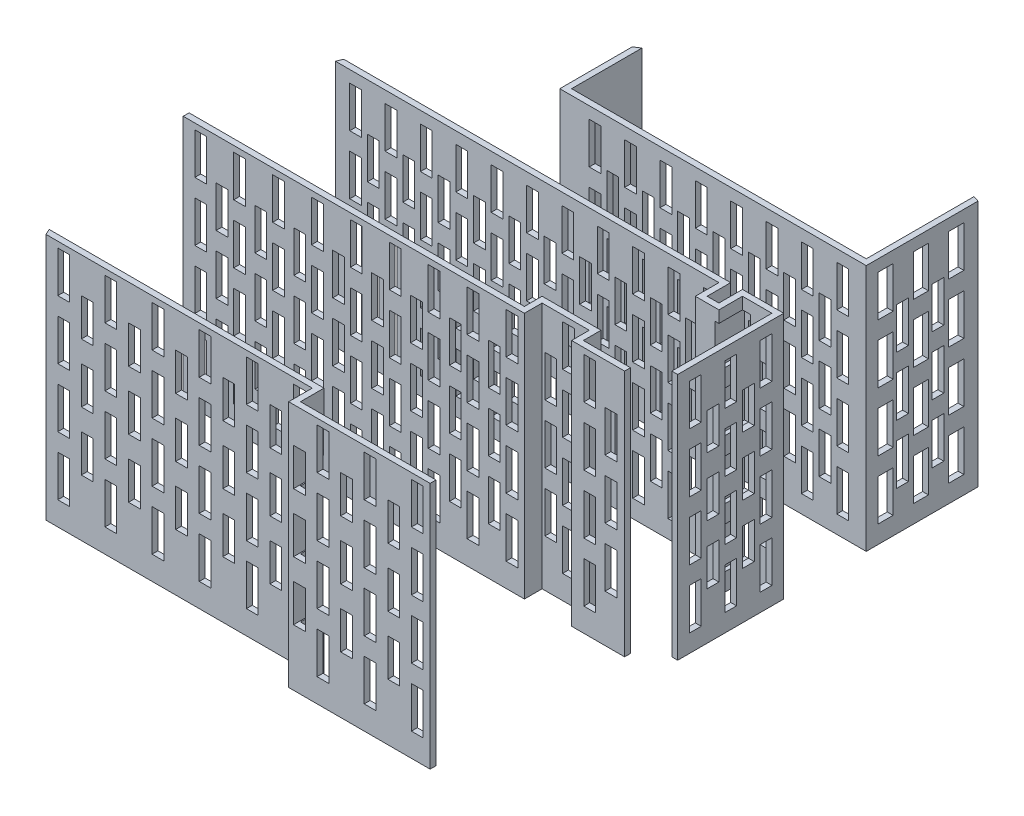
SolidWorks part; units mm, degrees
ref_plane "前视基准面" through (0, 0, 0) normal (0, 0, 1) x (1, 0, 0)
ref_plane "上视基准面" through (0, 0, 0) normal (0, 1, 0) x (1, 0, 0)
ref_plane "右视基准面" through (0, 0, 0) normal (1, 0, 0) x (0, 0, -1)
sketch "草图1" plane through (0, 0, 0) normal (0, 1, 0) x (1, 0, 0)
  line L0 (9, 42.9063) -> (9, -40.9545) construction
  line L1 (-51.5032, -25) -> (46.7174, -25) construction
  line L2 (-16, 25.9663) -> (-16, 20)
  line L3 (-16, 20) -> (9, 20)
  line L4 (-27.5908, -13) -> (-5, -13)
  line L5 (-5, -13) -> (-5, -15)
  line L6 (-5, -15) -> (7, -15)
  line L7 (-28.0401, 12) -> (4.5, 12)
  line L8 (4.5, 12) -> (4.5, 10)
  line L9 (4.5, 10) -> (6.5, 10)
  line L10 (6.5, 10) -> (6.5, 12)
  line L11 (6.5, 12) -> (9, 12)
  line L12 (9, 12) -> (9, 3.5009)
  line L13 (7, 2) -> (3, 2)
  line L14 (3, 2) -> (3, 3.5)
  line L15 (3, 3.5) -> (-2, 3.5)
  line L16 (-2, 3.5) -> (-2, 2)
  line L17 (-2, 2) -> (-30.4344, 2)
  line L18 (9, 20) -> (9, 29.1419)
  line L19 (-16.5, 25.6515) -> (-16.5, 19.5)
  line L20 (-16.5, 19.5) -> (9.5, 19.5)
  line L21 (9.5, 19.5) -> (9.5, 28.9828)
  line L22 (-16.5, 25.9663) -> (-16.5, 19.5) construction
  line L23 (9.5, 19.5) -> (9.5, 29.1419) construction
  line L24 (9, 29.1419) -> (9.5, 28.9828)
  line L25 (7, 3.5009) -> (9, 3.5009) construction
  line L26 (7, 3.5009) -> (7, 2) construction
  line L27 (7, -16.4991) -> (9, -16.4991) construction
  line L28 (7, -6.5) -> (19.2918, -6.5)
  line L29 (7, -15) -> (7, -16.4991) construction
  line L30 (-27.8209, 12.5) -> (5, 12.5)
  line L31 (5, 12.5) -> (5, 10.5)
  line L32 (5, 10.5) -> (6, 10.5)
  line L33 (6, 10.5) -> (6, 12.5)
  line L34 (6, 12.5) -> (9.5, 12.5)
  line L35 (9.5, 12.5) -> (9.5, 3.5009)
  line L36 (7, 1.5) -> (2.5, 1.5)
  line L37 (2.5, 1.5) -> (2.5, 3)
  line L38 (2.5, 3) -> (-1.5, 3)
  line L39 (-1.5, 3) -> (-1.5, 1.5)
  line L40 (-1.5, 1.5) -> (-30.4631, 1.5)
  line L41 (9, 3.5009) -> (9.5, 3.5009)
  line L42 (7, 1.5) -> (7, 2)
  line L43 (-28.0401, 12.5) -> (5, 12.5) construction
  line L44 (-1.5, 1.5) -> (-30.4344, 1.5) construction
  line L45 (-27.8209, -12.5) -> (-4.5, -12.5)
  line L46 (-4.5, -12.5) -> (-4.5, -14.5)
  line L47 (-4.5, -14.5) -> (7, -14.5)
  line L48 (7, -14.5) -> (7, -15)
  line L49 (-27.5908, -12.5) -> (-4.5, -12.5) construction
  arc A0 (-16, 25.9663) -> (-16.5, 25.6515) centre (0, 0) ccw
  arc A1 (-27.8209, -12.5) -> (-27.5908, -13) centre (0, 0) ccw
  arc A2 (-30.4344, 2) -> (-30.4631, 1.5) centre (0, 0) ccw
  arc A3 (-27.8209, 12.5) -> (-28.0401, 12) centre (0, 0) ccw
  dimension "D1" = 61
  dimension "D2" = 9
  dimension "D3" = 25
  dimension "D4" = 25
  dimension "D5" = 45
  dimension "D6" = 14
  dimension "D7" = 12
  dimension "D8" = 10
  dimension "D9" = 15
  dimension "D10" = 1.5
  dimension "D11" = 5
  dimension "D12" = 6
  dimension "D13" = 2
  dimension "D14" = 2
  dimension "D15" = 2.5
  dimension "D16" = 10
  dimension "D18" = 9.4828
  dimension "D19" = 6.5
  dimension "D20" = 10.0009
  dimension "D21" = 2
  dimension "D22" = 9.9991
  dimension "D17" = 0.5
  dimension "D23" = 0.5
  dimension "D24" = 0.5
extrude "凸台-拉伸1" add sketch "草图1" along normal blind 21 contours L6 L48 L47 L46 L45 A1 L4 L5 | L15 L16 L17 A2 L40 L39 L38 L37 L36 L42 L13 L14 | L35 L41 L12 L11 L10 L9 L8 L7 A3 L30 L31 L32 L33 L34 | L20 L21 L24 L18 L3 L2 A0 L19
sketch "草图3" plane through (0, 0, 15) normal (0, 0, 1) x (1, 0, 0)
  line L0 (-27.5908, 21) -> (-5, 21) construction
  line L1 (-26.5908, 20.5) -> (-25.5908, 20.5)
  line L2 (-26.5908, 20.5) -> (-26.5908, 17)
  line L3 (-26.5908, 17) -> (-25.5908, 17)
  line L4 (-25.5908, 20.5) -> (-25.5908, 17)
  line L5 (-27.5908, 21) -> (-27.5908, 0) construction
  line L6 (-22.5908, 20.5) -> (-22.5908, 17)
  line L7 (-22.5908, 20.5) -> (-21.5908, 20.5)
  line L8 (-21.5908, 20.5) -> (-21.5908, 17)
  line L9 (-22.5908, 17) -> (-21.5908, 17)
  line L10 (-18.5908, 20.5) -> (-18.5908, 17)
  line L11 (-18.5908, 20.5) -> (-17.5908, 20.5)
  line L12 (-17.5908, 20.5) -> (-17.5908, 17)
  line L13 (-18.5908, 17) -> (-17.5908, 17)
  line L14 (-14.5908, 20.5) -> (-14.5908, 17)
  line L15 (-14.5908, 20.5) -> (-13.5908, 20.5)
  line L16 (-13.5908, 20.5) -> (-13.5908, 17)
  line L17 (-14.5908, 17) -> (-13.5908, 17)
  line L18 (-10.5908, 20.5) -> (-10.5908, 17)
  line L19 (-10.5908, 20.5) -> (-9.5908, 20.5)
  line L20 (-9.5908, 20.5) -> (-9.5908, 17)
  line L21 (-10.5908, 17) -> (-9.5908, 17)
  line L22 (-6.5908, 20.5) -> (-6.5908, 17)
  line L23 (-6.5908, 20.5) -> (-5.5908, 20.5)
  line L24 (-5.5908, 20.5) -> (-5.5908, 17)
  line L25 (-6.5908, 17) -> (-5.5908, 17)
  line L26 (-2.5908, 20.5) -> (-2.5908, 17)
  line L27 (-2.5908, 20.5) -> (-1.5908, 20.5)
  line L28 (-1.5908, 20.5) -> (-1.5908, 17)
  line L29 (-2.5908, 17) -> (-1.5908, 17)
  line L30 (1.4092, 20.5) -> (1.4092, 17)
  line L31 (1.4092, 20.5) -> (2.4092, 20.5)
  line L32 (2.4092, 20.5) -> (2.4092, 17)
  line L33 (1.4092, 17) -> (2.4092, 17)
  line L34 (5.4092, 20.5) -> (5.4092, 17)
  line L35 (5.4092, 20.5) -> (6.4092, 20.5)
  line L36 (6.4092, 20.5) -> (6.4092, 17)
  line L37 (5.4092, 17) -> (6.4092, 17)
  line L38 (-26.5908, 15.5) -> (-26.5908, 12)
  line L39 (-26.5908, 15.5) -> (-25.5908, 15.5)
  line L40 (-25.5908, 15.5) -> (-25.5908, 12)
  line L41 (-26.5908, 12) -> (-25.5908, 12)
  line L42 (-22.5908, 15.5) -> (-22.5908, 12)
  line L43 (-22.5908, 12) -> (-21.5908, 12)
  line L44 (-21.5908, 15.5) -> (-21.5908, 12)
  line L45 (-22.5908, 15.5) -> (-21.5908, 15.5)
  line L46 (-18.5908, 15.5) -> (-18.5908, 12)
  line L47 (-18.5908, 12) -> (-17.5908, 12)
  line L48 (-17.5908, 15.5) -> (-17.5908, 12)
  line L49 (-18.5908, 15.5) -> (-17.5908, 15.5)
  line L50 (-14.5908, 15.5) -> (-14.5908, 12)
  line L51 (-14.5908, 12) -> (-13.5908, 12)
  line L52 (-13.5908, 15.5) -> (-13.5908, 12)
  line L53 (-14.5908, 15.5) -> (-13.5908, 15.5)
  line L54 (-10.5908, 15.5) -> (-10.5908, 12)
  line L55 (-10.5908, 12) -> (-9.5908, 12)
  line L56 (-9.5908, 15.5) -> (-9.5908, 12)
  line L57 (-10.5908, 15.5) -> (-9.5908, 15.5)
  line L58 (-6.5908, 15.5) -> (-6.5908, 12)
  line L59 (-6.5908, 12) -> (-5.5908, 12)
  line L60 (-5.5908, 15.5) -> (-5.5908, 12)
  line L61 (-6.5908, 15.5) -> (-5.5908, 15.5)
  line L62 (-2.5908, 15.5) -> (-2.5908, 12)
  line L63 (-2.5908, 12) -> (-1.5908, 12)
  line L64 (-1.5908, 15.5) -> (-1.5908, 12)
  line L65 (-2.5908, 15.5) -> (-1.5908, 15.5)
  line L66 (1.4092, 15.5) -> (1.4092, 12)
  line L67 (1.4092, 12) -> (2.4092, 12)
  line L68 (2.4092, 15.5) -> (2.4092, 12)
  line L69 (1.4092, 15.5) -> (2.4092, 15.5)
  line L70 (5.4092, 15.5) -> (5.4092, 12)
  line L71 (5.4092, 12) -> (6.4092, 12)
  line L72 (6.4092, 15.5) -> (6.4092, 12)
  line L73 (5.4092, 15.5) -> (6.4092, 15.5)
  line L74 (-26.5908, 10.5) -> (-26.5908, 7)
  line L75 (-26.5908, 10.5) -> (-25.5908, 10.5)
  line L76 (-25.5908, 10.5) -> (-25.5908, 7)
  line L77 (-26.5908, 7) -> (-25.5908, 7)
  line L78 (-22.5908, 10.5) -> (-22.5908, 7)
  line L79 (-22.5908, 7) -> (-21.5908, 7)
  line L80 (-21.5908, 10.5) -> (-21.5908, 7)
  line L81 (-22.5908, 10.5) -> (-21.5908, 10.5)
  line L82 (-18.5908, 10.5) -> (-18.5908, 7)
  line L83 (-18.5908, 7) -> (-17.5908, 7)
  line L84 (-17.5908, 10.5) -> (-17.5908, 7)
  line L85 (-18.5908, 10.5) -> (-17.5908, 10.5)
  line L86 (-14.5908, 10.5) -> (-14.5908, 7)
  line L87 (-14.5908, 7) -> (-13.5908, 7)
  line L88 (-13.5908, 10.5) -> (-13.5908, 7)
  line L89 (-14.5908, 10.5) -> (-13.5908, 10.5)
  line L90 (-10.5908, 10.5) -> (-10.5908, 7)
  line L91 (-10.5908, 7) -> (-9.5908, 7)
  line L92 (-9.5908, 10.5) -> (-9.5908, 7)
  line L93 (-10.5908, 10.5) -> (-9.5908, 10.5)
  line L94 (-6.5908, 10.5) -> (-6.5908, 7)
  line L95 (-6.5908, 7) -> (-5.5908, 7)
  line L96 (-5.5908, 10.5) -> (-5.5908, 7)
  line L97 (-6.5908, 10.5) -> (-5.5908, 10.5)
  line L98 (-2.5908, 10.5) -> (-2.5908, 7)
  line L99 (-2.5908, 7) -> (-1.5908, 7)
  line L100 (-1.5908, 10.5) -> (-1.5908, 7)
  line L101 (-2.5908, 10.5) -> (-1.5908, 10.5)
  line L102 (1.4092, 10.5) -> (1.4092, 7)
  line L103 (1.4092, 7) -> (2.4092, 7)
  line L104 (2.4092, 10.5) -> (2.4092, 7)
  line L105 (1.4092, 10.5) -> (2.4092, 10.5)
  line L106 (5.4092, 10.5) -> (5.4092, 7)
  line L107 (5.4092, 7) -> (6.4092, 7)
  line L108 (6.4092, 10.5) -> (6.4092, 7)
  line L109 (5.4092, 10.5) -> (6.4092, 10.5)
  line L110 (-26.5908, 5.5) -> (-26.5908, 2)
  line L111 (-26.5908, 5.5) -> (-25.5908, 5.5)
  line L112 (-25.5908, 5.5) -> (-25.5908, 2)
  line L113 (-26.5908, 2) -> (-25.5908, 2)
  line L114 (-22.5908, 5.5) -> (-22.5908, 2)
  line L115 (-22.5908, 2) -> (-21.5908, 2)
  line L116 (-21.5908, 5.5) -> (-21.5908, 2)
  line L117 (-22.5908, 5.5) -> (-21.5908, 5.5)
  line L118 (-18.5908, 5.5) -> (-18.5908, 2)
  line L119 (-18.5908, 2) -> (-17.5908, 2)
  line L120 (-17.5908, 5.5) -> (-17.5908, 2)
  line L121 (-18.5908, 5.5) -> (-17.5908, 5.5)
  line L122 (-14.5908, 5.5) -> (-14.5908, 2)
  line L123 (-14.5908, 2) -> (-13.5908, 2)
  line L124 (-13.5908, 5.5) -> (-13.5908, 2)
  line L125 (-14.5908, 5.5) -> (-13.5908, 5.5)
  line L126 (-10.5908, 5.5) -> (-10.5908, 2)
  line L127 (-10.5908, 2) -> (-9.5908, 2)
  line L128 (-9.5908, 5.5) -> (-9.5908, 2)
  line L129 (-10.5908, 5.5) -> (-9.5908, 5.5)
  line L130 (-6.5908, 5.5) -> (-6.5908, 2)
  line L131 (-6.5908, 2) -> (-5.5908, 2)
  line L132 (-5.5908, 5.5) -> (-5.5908, 2)
  line L133 (-6.5908, 5.5) -> (-5.5908, 5.5)
  line L134 (-2.5908, 5.5) -> (-2.5908, 2)
  line L135 (-2.5908, 2) -> (-1.5908, 2)
  line L136 (-1.5908, 5.5) -> (-1.5908, 2)
  line L137 (-2.5908, 5.5) -> (-1.5908, 5.5)
  line L138 (1.4092, 5.5) -> (1.4092, 2)
  line L139 (1.4092, 2) -> (2.4092, 2)
  line L140 (2.4092, 5.5) -> (2.4092, 2)
  line L141 (1.4092, 5.5) -> (2.4092, 5.5)
  line L142 (5.4092, 5.5) -> (5.4092, 2)
  line L143 (5.4092, 2) -> (6.4092, 2)
  line L144 (6.4092, 5.5) -> (6.4092, 2)
  line L145 (5.4092, 5.5) -> (6.4092, 5.5)
  line L146 (-20.5908, 18) -> (-20.5908, 14.8162)
  line L147 (-24.5908, 18) -> (-23.5908, 18)
  line L148 (-24.5908, 18) -> (-24.5908, 14.8162)
  line L149 (-24.5908, 14.8162) -> (-23.5908, 14.8162)
  line L150 (-23.5908, 18) -> (-23.5908, 14.8162)
  line L151 (-20.5908, 18) -> (-19.5908, 18)
  line L152 (-19.5908, 18) -> (-19.5908, 14.8162)
  line L153 (-20.5908, 14.8162) -> (-19.5908, 14.8162)
  line L154 (-16.5908, 18) -> (-16.5908, 14.8162)
  line L155 (-16.5908, 18) -> (-15.5908, 18)
  line L156 (-15.5908, 18) -> (-15.5908, 14.8162)
  line L157 (-16.5908, 14.8162) -> (-15.5908, 14.8162)
  line L158 (-12.5908, 18) -> (-12.5908, 14.8162)
  line L159 (-12.5908, 18) -> (-11.5908, 18)
  line L160 (-11.5908, 18) -> (-11.5908, 14.8162)
  line L161 (-12.5908, 14.8162) -> (-11.5908, 14.8162)
  line L162 (-8.5908, 18) -> (-8.5908, 14.8162)
  line L163 (-8.5908, 18) -> (-7.5908, 18)
  line L164 (-7.5908, 18) -> (-7.5908, 14.8162)
  line L165 (-8.5908, 14.8162) -> (-7.5908, 14.8162)
  line L166 (-4.5908, 18) -> (-4.5908, 14.8162)
  line L167 (-4.5908, 18) -> (-3.5908, 18)
  line L168 (-3.5908, 18) -> (-3.5908, 14.8162)
  line L169 (-4.5908, 14.8162) -> (-3.5908, 14.8162)
  line L170 (-0.5908, 18) -> (-0.5908, 14.8162)
  line L171 (-0.5908, 18) -> (0.4092, 18)
  line L172 (0.4092, 18) -> (0.4092, 14.8162)
  line L173 (-0.5908, 14.8162) -> (0.4092, 14.8162)
  line L174 (3.4092, 18) -> (3.4092, 14.8162)
  line L175 (3.4092, 18) -> (4.4092, 18)
  line L176 (4.4092, 18) -> (4.4092, 14.8162)
  line L177 (3.4092, 14.8162) -> (4.4092, 14.8162)
  line L178 (-24.5908, 13) -> (-24.5908, 9.8162)
  line L179 (-24.5908, 13) -> (-23.5908, 13)
  line L180 (-23.5908, 13) -> (-23.5908, 9.8162)
  line L181 (-24.5908, 9.8162) -> (-23.5908, 9.8162)
  line L182 (-20.5908, 13) -> (-20.5908, 9.8162)
  line L183 (-20.5908, 9.8162) -> (-19.5908, 9.8162)
  line L184 (-19.5908, 13) -> (-19.5908, 9.8162)
  line L185 (-20.5908, 13) -> (-19.5908, 13)
  line L186 (-16.5908, 13) -> (-16.5908, 9.8162)
  line L187 (-16.5908, 9.8162) -> (-15.5908, 9.8162)
  line L188 (-15.5908, 13) -> (-15.5908, 9.8162)
  line L189 (-16.5908, 13) -> (-15.5908, 13)
  line L190 (-12.5908, 13) -> (-12.5908, 9.8162)
  line L191 (-12.5908, 9.8162) -> (-11.5908, 9.8162)
  line L192 (-11.5908, 13) -> (-11.5908, 9.8162)
  line L193 (-12.5908, 13) -> (-11.5908, 13)
  line L194 (-8.5908, 13) -> (-8.5908, 9.8162)
  line L195 (-8.5908, 9.8162) -> (-7.5908, 9.8162)
  line L196 (-7.5908, 13) -> (-7.5908, 9.8162)
  line L197 (-8.5908, 13) -> (-7.5908, 13)
  line L198 (-4.5908, 13) -> (-4.5908, 9.8162)
  line L199 (-4.5908, 9.8162) -> (-3.5908, 9.8162)
  line L200 (-3.5908, 13) -> (-3.5908, 9.8162)
  line L201 (-4.5908, 13) -> (-3.5908, 13)
  line L202 (-0.5908, 13) -> (-0.5908, 9.8162)
  line L203 (-0.5908, 9.8162) -> (0.4092, 9.8162)
  line L204 (0.4092, 13) -> (0.4092, 9.8162)
  line L205 (-0.5908, 13) -> (0.4092, 13)
  line L206 (3.4092, 13) -> (3.4092, 9.8162)
  line L207 (3.4092, 9.8162) -> (4.4092, 9.8162)
  line L208 (4.4092, 13) -> (4.4092, 9.8162)
  line L209 (3.4092, 13) -> (4.4092, 13)
  line L210 (-24.5908, 8) -> (-24.5908, 4.8162)
  line L211 (-24.5908, 8) -> (-23.5908, 8)
  line L212 (-23.5908, 8) -> (-23.5908, 4.8162)
  line L213 (-24.5908, 4.8162) -> (-23.5908, 4.8162)
  line L214 (-20.5908, 8) -> (-20.5908, 4.8162)
  line L215 (-20.5908, 4.8162) -> (-19.5908, 4.8162)
  line L216 (-19.5908, 8) -> (-19.5908, 4.8162)
  line L217 (-20.5908, 8) -> (-19.5908, 8)
  line L218 (-16.5908, 8) -> (-16.5908, 4.8162)
  line L219 (-16.5908, 4.8162) -> (-15.5908, 4.8162)
  line L220 (-15.5908, 8) -> (-15.5908, 4.8162)
  line L221 (-16.5908, 8) -> (-15.5908, 8)
  line L222 (-12.5908, 8) -> (-12.5908, 4.8162)
  line L223 (-12.5908, 4.8162) -> (-11.5908, 4.8162)
  line L224 (-11.5908, 8) -> (-11.5908, 4.8162)
  line L225 (-12.5908, 8) -> (-11.5908, 8)
  line L226 (-8.5908, 8) -> (-8.5908, 4.8162)
  line L227 (-8.5908, 4.8162) -> (-7.5908, 4.8162)
  line L228 (-7.5908, 8) -> (-7.5908, 4.8162)
  line L229 (-8.5908, 8) -> (-7.5908, 8)
  line L230 (-4.5908, 8) -> (-4.5908, 4.8162)
  line L231 (-4.5908, 4.8162) -> (-3.5908, 4.8162)
  line L232 (-3.5908, 8) -> (-3.5908, 4.8162)
  line L233 (-4.5908, 8) -> (-3.5908, 8)
  line L234 (-0.5908, 8) -> (-0.5908, 4.8162)
  line L235 (-0.5908, 4.8162) -> (0.4092, 4.8162)
  line L236 (0.4092, 8) -> (0.4092, 4.8162)
  line L237 (-0.5908, 8) -> (0.4092, 8)
  line L238 (3.4092, 8) -> (3.4092, 4.8162)
  line L239 (3.4092, 4.8162) -> (4.4092, 4.8162)
  line L240 (4.4092, 8) -> (4.4092, 4.8162)
  line L241 (3.4092, 8) -> (4.4092, 8)
  dimension "D1" = 1
  dimension "D2" = 3.5
  dimension "D3" = 0.5
  dimension "D4" = 1
  dimension "D7" = 3.1838
  dimension "D8" = 1
  dimension "D9" = 1
  dimension "D10" = 1
  dimension "D5" = 9
  dimension "D6" = 4
  dimension "D11" = 8
  dimension "D12" = 3
extrude "切除-拉伸1" cut sketch "草图3" against normal blind 5
sketch "草图4" plane through (0, 0, -1.5) normal (0, 0, 1) x (1, 0, 0)
  line L0 (-30.4631, 21) -> (-30.4631, 0) construction
  line L1 (-29.4631, 20.5) -> (-28.4631, 20.5)
  line L2 (-29.4631, 20.5) -> (-29.4631, 17)
  line L3 (-29.4631, 17) -> (-28.4631, 17)
  line L4 (-28.4631, 20.5) -> (-28.4631, 17)
  line L5 (-1.5, 21) -> (-30.4631, 21) construction
  line L6 (-26.1631, 20.5) -> (-26.1631, 17)
  line L7 (-26.1631, 20.5) -> (-25.1631, 20.5)
  line L8 (-25.1631, 20.5) -> (-25.1631, 17)
  line L9 (-26.1631, 17) -> (-25.1631, 17)
  line L10 (-22.8631, 20.5) -> (-22.8631, 17)
  line L11 (-22.8631, 20.5) -> (-21.8631, 20.5)
  line L12 (-21.8631, 20.5) -> (-21.8631, 17)
  line L13 (-22.8631, 17) -> (-21.8631, 17)
  line L14 (-19.5631, 20.5) -> (-19.5631, 17)
  line L15 (-19.5631, 20.5) -> (-18.5631, 20.5)
  line L16 (-18.5631, 20.5) -> (-18.5631, 17)
  line L17 (-19.5631, 17) -> (-18.5631, 17)
  line L18 (-16.2631, 20.5) -> (-16.2631, 17)
  line L19 (-16.2631, 20.5) -> (-15.2631, 20.5)
  line L20 (-15.2631, 20.5) -> (-15.2631, 17)
  line L21 (-16.2631, 17) -> (-15.2631, 17)
  line L22 (-12.9631, 20.5) -> (-12.9631, 17)
  line L23 (-12.9631, 20.5) -> (-11.9631, 20.5)
  line L24 (-11.9631, 20.5) -> (-11.9631, 17)
  line L25 (-12.9631, 17) -> (-11.9631, 17)
  line L26 (-9.6631, 20.5) -> (-9.6631, 17)
  line L27 (-9.6631, 20.5) -> (-8.6631, 20.5)
  line L28 (-8.6631, 20.5) -> (-8.6631, 17)
  line L29 (-9.6631, 17) -> (-8.6631, 17)
  line L30 (-6.3631, 20.5) -> (-6.3631, 17)
  line L31 (-6.3631, 20.5) -> (-5.3631, 20.5)
  line L32 (-5.3631, 20.5) -> (-5.3631, 17)
  line L33 (-6.3631, 17) -> (-5.3631, 17)
  line L34 (-3.0631, 20.5) -> (-3.0631, 17)
  line L35 (-3.0631, 20.5) -> (-2.0631, 20.5)
  line L36 (-2.0631, 20.5) -> (-2.0631, 17)
  line L37 (-3.0631, 17) -> (-2.0631, 17)
  line L38 (0.2369, 20.5) -> (0.2369, 17)
  line L39 (0.2369, 20.5) -> (1.2369, 20.5)
  line L40 (1.2369, 20.5) -> (1.2369, 17)
  line L41 (0.2369, 17) -> (1.2369, 17)
  line L42 (3.5369, 20.5) -> (3.5369, 17)
  line L43 (3.5369, 20.5) -> (4.5369, 20.5)
  line L44 (4.5369, 20.5) -> (4.5369, 17)
  line L45 (3.5369, 17) -> (4.5369, 17)
  line L46 (-29.4631, 15.5) -> (-29.4631, 12)
  line L47 (-29.4631, 15.5) -> (-28.4631, 15.5)
  line L48 (-28.4631, 15.5) -> (-28.4631, 12)
  line L49 (-29.4631, 12) -> (-28.4631, 12)
  line L50 (-26.1631, 15.5) -> (-26.1631, 12)
  line L51 (-26.1631, 12) -> (-25.1631, 12)
  line L52 (-25.1631, 15.5) -> (-25.1631, 12)
  line L53 (-26.1631, 15.5) -> (-25.1631, 15.5)
  line L54 (-22.8631, 15.5) -> (-22.8631, 12)
  line L55 (-22.8631, 12) -> (-21.8631, 12)
  line L56 (-21.8631, 15.5) -> (-21.8631, 12)
  line L57 (-22.8631, 15.5) -> (-21.8631, 15.5)
  line L58 (-19.5631, 15.5) -> (-19.5631, 12)
  line L59 (-19.5631, 12) -> (-18.5631, 12)
  line L60 (-18.5631, 15.5) -> (-18.5631, 12)
  line L61 (-19.5631, 15.5) -> (-18.5631, 15.5)
  line L62 (-16.2631, 15.5) -> (-16.2631, 12)
  line L63 (-16.2631, 12) -> (-15.2631, 12)
  line L64 (-15.2631, 15.5) -> (-15.2631, 12)
  line L65 (-16.2631, 15.5) -> (-15.2631, 15.5)
  line L66 (-12.9631, 15.5) -> (-12.9631, 12)
  line L67 (-12.9631, 12) -> (-11.9631, 12)
  line L68 (-11.9631, 15.5) -> (-11.9631, 12)
  line L69 (-12.9631, 15.5) -> (-11.9631, 15.5)
  line L70 (-9.6631, 15.5) -> (-9.6631, 12)
  line L71 (-9.6631, 12) -> (-8.6631, 12)
  line L72 (-8.6631, 15.5) -> (-8.6631, 12)
  line L73 (-9.6631, 15.5) -> (-8.6631, 15.5)
  line L74 (-6.3631, 15.5) -> (-6.3631, 12)
  line L75 (-6.3631, 12) -> (-5.3631, 12)
  line L76 (-5.3631, 15.5) -> (-5.3631, 12)
  line L77 (-6.3631, 15.5) -> (-5.3631, 15.5)
  line L78 (-3.0631, 15.5) -> (-3.0631, 12)
  line L79 (-3.0631, 12) -> (-2.0631, 12)
  line L80 (-2.0631, 15.5) -> (-2.0631, 12)
  line L81 (-3.0631, 15.5) -> (-2.0631, 15.5)
  line L82 (0.2369, 15.5) -> (0.2369, 12)
  line L83 (0.2369, 12) -> (1.2369, 12)
  line L84 (1.2369, 15.5) -> (1.2369, 12)
  line L85 (0.2369, 15.5) -> (1.2369, 15.5)
  line L86 (3.5369, 15.5) -> (3.5369, 12)
  line L87 (3.5369, 12) -> (4.5369, 12)
  line L88 (4.5369, 15.5) -> (4.5369, 12)
  line L89 (3.5369, 15.5) -> (4.5369, 15.5)
  line L90 (-29.4631, 10.5) -> (-29.4631, 7)
  line L91 (-29.4631, 10.5) -> (-28.4631, 10.5)
  line L92 (-28.4631, 10.5) -> (-28.4631, 7)
  line L93 (-29.4631, 7) -> (-28.4631, 7)
  line L94 (-26.1631, 10.5) -> (-26.1631, 7)
  line L95 (-26.1631, 7) -> (-25.1631, 7)
  line L96 (-25.1631, 10.5) -> (-25.1631, 7)
  line L97 (-26.1631, 10.5) -> (-25.1631, 10.5)
  line L98 (-22.8631, 10.5) -> (-22.8631, 7)
  line L99 (-22.8631, 7) -> (-21.8631, 7)
  line L100 (-21.8631, 10.5) -> (-21.8631, 7)
  line L101 (-22.8631, 10.5) -> (-21.8631, 10.5)
  line L102 (-19.5631, 10.5) -> (-19.5631, 7)
  line L103 (-19.5631, 7) -> (-18.5631, 7)
  line L104 (-18.5631, 10.5) -> (-18.5631, 7)
  line L105 (-19.5631, 10.5) -> (-18.5631, 10.5)
  line L106 (-16.2631, 10.5) -> (-16.2631, 7)
  line L107 (-16.2631, 7) -> (-15.2631, 7)
  line L108 (-15.2631, 10.5) -> (-15.2631, 7)
  line L109 (-16.2631, 10.5) -> (-15.2631, 10.5)
  line L110 (-12.9631, 10.5) -> (-12.9631, 7)
  line L111 (-12.9631, 7) -> (-11.9631, 7)
  line L112 (-11.9631, 10.5) -> (-11.9631, 7)
  line L113 (-12.9631, 10.5) -> (-11.9631, 10.5)
  line L114 (-9.6631, 10.5) -> (-9.6631, 7)
  line L115 (-9.6631, 7) -> (-8.6631, 7)
  line L116 (-8.6631, 10.5) -> (-8.6631, 7)
  line L117 (-9.6631, 10.5) -> (-8.6631, 10.5)
  line L118 (-6.3631, 10.5) -> (-6.3631, 7)
  line L119 (-6.3631, 7) -> (-5.3631, 7)
  line L120 (-5.3631, 10.5) -> (-5.3631, 7)
  line L121 (-6.3631, 10.5) -> (-5.3631, 10.5)
  line L122 (-3.0631, 10.5) -> (-3.0631, 7)
  line L123 (-3.0631, 7) -> (-2.0631, 7)
  line L124 (-2.0631, 10.5) -> (-2.0631, 7)
  line L125 (-3.0631, 10.5) -> (-2.0631, 10.5)
  line L126 (0.2369, 10.5) -> (0.2369, 7)
  line L127 (0.2369, 7) -> (1.2369, 7)
  line L128 (1.2369, 10.5) -> (1.2369, 7)
  line L129 (0.2369, 10.5) -> (1.2369, 10.5)
  line L130 (3.5369, 10.5) -> (3.5369, 7)
  line L131 (3.5369, 7) -> (4.5369, 7)
  line L132 (4.5369, 10.5) -> (4.5369, 7)
  line L133 (3.5369, 10.5) -> (4.5369, 10.5)
  line L134 (-29.4631, 5.5) -> (-29.4631, 2)
  line L135 (-29.4631, 5.5) -> (-28.4631, 5.5)
  line L136 (-28.4631, 5.5) -> (-28.4631, 2)
  line L137 (-29.4631, 2) -> (-28.4631, 2)
  line L138 (-26.1631, 5.5) -> (-26.1631, 2)
  line L139 (-26.1631, 2) -> (-25.1631, 2)
  line L140 (-25.1631, 5.5) -> (-25.1631, 2)
  line L141 (-26.1631, 5.5) -> (-25.1631, 5.5)
  line L142 (-22.8631, 5.5) -> (-22.8631, 2)
  line L143 (-22.8631, 2) -> (-21.8631, 2)
  line L144 (-21.8631, 5.5) -> (-21.8631, 2)
  line L145 (-22.8631, 5.5) -> (-21.8631, 5.5)
  line L146 (-19.5631, 5.5) -> (-19.5631, 2)
  line L147 (-19.5631, 2) -> (-18.5631, 2)
  line L148 (-18.5631, 5.5) -> (-18.5631, 2)
  line L149 (-19.5631, 5.5) -> (-18.5631, 5.5)
  line L150 (-16.2631, 5.5) -> (-16.2631, 2)
  line L151 (-16.2631, 2) -> (-15.2631, 2)
  line L152 (-15.2631, 5.5) -> (-15.2631, 2)
  line L153 (-16.2631, 5.5) -> (-15.2631, 5.5)
  line L154 (-12.9631, 5.5) -> (-12.9631, 2)
  line L155 (-12.9631, 2) -> (-11.9631, 2)
  line L156 (-11.9631, 5.5) -> (-11.9631, 2)
  line L157 (-12.9631, 5.5) -> (-11.9631, 5.5)
  line L158 (-9.6631, 5.5) -> (-9.6631, 2)
  line L159 (-9.6631, 2) -> (-8.6631, 2)
  line L160 (-8.6631, 5.5) -> (-8.6631, 2)
  line L161 (-9.6631, 5.5) -> (-8.6631, 5.5)
  line L162 (-6.3631, 5.5) -> (-6.3631, 2)
  line L163 (-6.3631, 2) -> (-5.3631, 2)
  line L164 (-5.3631, 5.5) -> (-5.3631, 2)
  line L165 (-6.3631, 5.5) -> (-5.3631, 5.5)
  line L166 (-3.0631, 5.5) -> (-3.0631, 2)
  line L167 (-3.0631, 2) -> (-2.0631, 2)
  line L168 (-2.0631, 5.5) -> (-2.0631, 2)
  line L169 (-3.0631, 5.5) -> (-2.0631, 5.5)
  line L170 (0.2369, 5.5) -> (0.2369, 2)
  line L171 (0.2369, 2) -> (1.2369, 2)
  line L172 (1.2369, 5.5) -> (1.2369, 2)
  line L173 (0.2369, 5.5) -> (1.2369, 5.5)
  line L174 (3.5369, 5.5) -> (3.5369, 2)
  line L175 (3.5369, 2) -> (4.5369, 2)
  line L176 (4.5369, 5.5) -> (4.5369, 2)
  line L177 (3.5369, 5.5) -> (4.5369, 5.5)
  line L178 (-24.3631, 17.5) -> (-24.3631, 14)
  line L179 (-27.6631, 17.5) -> (-26.6631, 17.5)
  line L180 (-27.6631, 17.5) -> (-27.6631, 14)
  line L181 (-27.6631, 14) -> (-26.6631, 14)
  line L182 (-26.6631, 17.5) -> (-26.6631, 14)
  line L183 (-24.3631, 17.5) -> (-23.3631, 17.5)
  line L184 (-23.3631, 17.5) -> (-23.3631, 14)
  line L185 (-24.3631, 14) -> (-23.3631, 14)
  line L186 (-21.0631, 17.5) -> (-21.0631, 14)
  line L187 (-21.0631, 17.5) -> (-20.0631, 17.5)
  line L188 (-20.0631, 17.5) -> (-20.0631, 14)
  line L189 (-21.0631, 14) -> (-20.0631, 14)
  line L190 (-17.7631, 17.5) -> (-17.7631, 14)
  line L191 (-17.7631, 17.5) -> (-16.7631, 17.5)
  line L192 (-16.7631, 17.5) -> (-16.7631, 14)
  line L193 (-17.7631, 14) -> (-16.7631, 14)
  line L194 (-14.4631, 17.5) -> (-14.4631, 14)
  line L195 (-14.4631, 17.5) -> (-13.4631, 17.5)
  line L196 (-13.4631, 17.5) -> (-13.4631, 14)
  line L197 (-14.4631, 14) -> (-13.4631, 14)
  line L198 (-11.1631, 17.5) -> (-11.1631, 14)
  line L199 (-11.1631, 17.5) -> (-10.1631, 17.5)
  line L200 (-10.1631, 17.5) -> (-10.1631, 14)
  line L201 (-11.1631, 14) -> (-10.1631, 14)
  line L202 (-7.8631, 17.5) -> (-7.8631, 14)
  line L203 (-7.8631, 17.5) -> (-6.8631, 17.5)
  line L204 (-6.8631, 17.5) -> (-6.8631, 14)
  line L205 (-7.8631, 14) -> (-6.8631, 14)
  line L206 (-4.5631, 17.5) -> (-4.5631, 14)
  line L207 (-4.5631, 17.5) -> (-3.5631, 17.5)
  line L208 (-3.5631, 17.5) -> (-3.5631, 14)
  line L209 (-4.5631, 14) -> (-3.5631, 14)
  line L210 (-1.2631, 17.5) -> (-1.2631, 14)
  line L211 (-1.2631, 17.5) -> (-0.2631, 17.5)
  line L212 (-0.2631, 17.5) -> (-0.2631, 14)
  line L213 (-1.2631, 14) -> (-0.2631, 14)
  line L214 (2.0369, 17.5) -> (2.0369, 14) [skipped]
  line L215 (2.0369, 17.5) -> (3.0369, 17.5) [skipped]
  line L216 (3.0369, 17.5) -> (3.0369, 14) [skipped]
  line L217 (2.0369, 14) -> (3.0369, 14) [skipped]
  line L218 (5.3369, 17.5) -> (5.3369, 14)
  line L219 (5.3369, 17.5) -> (6.3369, 17.5)
  line L220 (6.3369, 17.5) -> (6.3369, 14)
  line L221 (5.3369, 14) -> (6.3369, 14)
  line L222 (-27.6631, 12.5) -> (-27.6631, 9)
  line L223 (-27.6631, 12.5) -> (-26.6631, 12.5)
  line L224 (-26.6631, 12.5) -> (-26.6631, 9)
  line L225 (-27.6631, 9) -> (-26.6631, 9)
  line L226 (-24.3631, 12.5) -> (-24.3631, 9)
  line L227 (-24.3631, 9) -> (-23.3631, 9)
  line L228 (-23.3631, 12.5) -> (-23.3631, 9)
  line L229 (-24.3631, 12.5) -> (-23.3631, 12.5)
  line L230 (-21.0631, 12.5) -> (-21.0631, 9)
  line L231 (-21.0631, 9) -> (-20.0631, 9)
  line L232 (-20.0631, 12.5) -> (-20.0631, 9)
  line L233 (-21.0631, 12.5) -> (-20.0631, 12.5)
  line L234 (-17.7631, 12.5) -> (-17.7631, 9)
  line L235 (-17.7631, 9) -> (-16.7631, 9)
  line L236 (-16.7631, 12.5) -> (-16.7631, 9)
  line L237 (-17.7631, 12.5) -> (-16.7631, 12.5)
  line L238 (-14.4631, 12.5) -> (-14.4631, 9)
  line L239 (-14.4631, 9) -> (-13.4631, 9)
  line L240 (-13.4631, 12.5) -> (-13.4631, 9)
  line L241 (-14.4631, 12.5) -> (-13.4631, 12.5)
  line L242 (-11.1631, 12.5) -> (-11.1631, 9)
  line L243 (-11.1631, 9) -> (-10.1631, 9)
  line L244 (-10.1631, 12.5) -> (-10.1631, 9)
  line L245 (-11.1631, 12.5) -> (-10.1631, 12.5)
  line L246 (-7.8631, 12.5) -> (-7.8631, 9)
  line L247 (-7.8631, 9) -> (-6.8631, 9)
  line L248 (-6.8631, 12.5) -> (-6.8631, 9)
  line L249 (-7.8631, 12.5) -> (-6.8631, 12.5)
  line L250 (-4.5631, 12.5) -> (-4.5631, 9)
  line L251 (-4.5631, 9) -> (-3.5631, 9)
  line L252 (-3.5631, 12.5) -> (-3.5631, 9)
  line L253 (-4.5631, 12.5) -> (-3.5631, 12.5)
  line L254 (-1.2631, 12.5) -> (-1.2631, 9)
  line L255 (-1.2631, 9) -> (-0.2631, 9)
  line L256 (-0.2631, 12.5) -> (-0.2631, 9)
  line L257 (-1.2631, 12.5) -> (-0.2631, 12.5)
  line L258 (5.3369, 12.5) -> (5.3369, 9)
  line L259 (5.3369, 9) -> (6.3369, 9)
  line L260 (6.3369, 12.5) -> (6.3369, 9)
  line L261 (5.3369, 12.5) -> (6.3369, 12.5)
  line L262 (-27.6631, 7.5) -> (-27.6631, 4)
  line L263 (-27.6631, 7.5) -> (-26.6631, 7.5)
  line L264 (-26.6631, 7.5) -> (-26.6631, 4)
  line L265 (-27.6631, 4) -> (-26.6631, 4)
  line L266 (-24.3631, 7.5) -> (-24.3631, 4)
  line L267 (-24.3631, 4) -> (-23.3631, 4)
  line L268 (-23.3631, 7.5) -> (-23.3631, 4)
  line L269 (-24.3631, 7.5) -> (-23.3631, 7.5)
  line L270 (-21.0631, 7.5) -> (-21.0631, 4)
  line L271 (-21.0631, 4) -> (-20.0631, 4)
  line L272 (-20.0631, 7.5) -> (-20.0631, 4)
  line L273 (-21.0631, 7.5) -> (-20.0631, 7.5)
  line L274 (-17.7631, 7.5) -> (-17.7631, 4)
  line L275 (-17.7631, 4) -> (-16.7631, 4)
  line L276 (-16.7631, 7.5) -> (-16.7631, 4)
  line L277 (-17.7631, 7.5) -> (-16.7631, 7.5)
  line L278 (-14.4631, 7.5) -> (-14.4631, 4)
  line L279 (-14.4631, 4) -> (-13.4631, 4)
  line L280 (-13.4631, 7.5) -> (-13.4631, 4)
  line L281 (-14.4631, 7.5) -> (-13.4631, 7.5)
  line L282 (-11.1631, 7.5) -> (-11.1631, 4)
  line L283 (-11.1631, 4) -> (-10.1631, 4)
  line L284 (-10.1631, 7.5) -> (-10.1631, 4)
  line L285 (-11.1631, 7.5) -> (-10.1631, 7.5)
  line L286 (-7.8631, 7.5) -> (-7.8631, 4)
  line L287 (-7.8631, 4) -> (-6.8631, 4)
  line L288 (-6.8631, 7.5) -> (-6.8631, 4)
  line L289 (-7.8631, 7.5) -> (-6.8631, 7.5)
  line L290 (-4.5631, 7.5) -> (-4.5631, 4)
  line L291 (-4.5631, 4) -> (-3.5631, 4)
  line L292 (-3.5631, 7.5) -> (-3.5631, 4)
  line L293 (-4.5631, 7.5) -> (-3.5631, 7.5)
  line L294 (-1.2631, 7.5) -> (-1.2631, 4)
  line L295 (-1.2631, 4) -> (-0.2631, 4)
  line L296 (-0.2631, 7.5) -> (-0.2631, 4)
  line L297 (-1.2631, 7.5) -> (-0.2631, 7.5)
  line L298 (5.3369, 7.5) -> (5.3369, 4)
  line L299 (5.3369, 4) -> (6.3369, 4)
  line L300 (6.3369, 7.5) -> (6.3369, 4)
  line L301 (5.3369, 7.5) -> (6.3369, 7.5)
  dimension "D1" = 3.5
  dimension "D2" = 1
  dimension "D3" = 1
  dimension "D4" = 0.5
  dimension "D7" = 1
  dimension "D8" = 3.5
  dimension "D9" = 0.8
  dimension "D10" = 0.5
  dimension "D5" = 11
  dimension "D6" = 4
  dimension "D11" = 11
  dimension "D12" = 3
extrude "切除-拉伸2" cut sketch "草图4" against normal blind 5
sketch "草图5" plane through (0, 0, -20) normal (0, 0, -1) x (-1, 0, 0)
  line L0 (16, 21) -> (-9, 21) construction
  line L1 (-8, 20) -> (-7, 20)
  line L2 (-8, 20) -> (-8, 16.5)
  line L3 (-8, 16.5) -> (-7, 16.5)
  line L4 (-7, 20) -> (-7, 16.5)
  line L5 (-9, 21) -> (-9, 0) construction
  line L6 (-5, 20) -> (-5, 16.5)
  line L7 (-5, 20) -> (-4, 20)
  line L8 (-4, 20) -> (-4, 16.5)
  line L9 (-5, 16.5) -> (-4, 16.5)
  line L10 (-2, 20) -> (-2, 16.5)
  line L11 (-2, 20) -> (-1, 20)
  line L12 (-1, 20) -> (-1, 16.5)
  line L13 (-2, 16.5) -> (-1, 16.5)
  line L14 (1, 20) -> (1, 16.5)
  line L15 (1, 20) -> (2, 20)
  line L16 (2, 20) -> (2, 16.5)
  line L17 (1, 16.5) -> (2, 16.5)
  line L18 (4, 20) -> (4, 16.5)
  line L19 (4, 20) -> (5, 20)
  line L20 (5, 20) -> (5, 16.5)
  line L21 (4, 16.5) -> (5, 16.5)
  line L22 (7, 20) -> (7, 16.5)
  line L23 (7, 20) -> (8, 20)
  line L24 (8, 20) -> (8, 16.5)
  line L25 (7, 16.5) -> (8, 16.5)
  line L26 (10, 20) -> (10, 16.5)
  line L27 (10, 20) -> (11, 20)
  line L28 (11, 20) -> (11, 16.5)
  line L29 (10, 16.5) -> (11, 16.5)
  line L30 (13, 20) -> (13, 16.5)
  line L31 (13, 20) -> (14, 20)
  line L32 (14, 20) -> (14, 16.5)
  line L33 (13, 16.5) -> (14, 16.5)
  line L34 (-8, 15) -> (-8, 11.5)
  line L35 (-8, 15) -> (-7, 15)
  line L36 (-7, 15) -> (-7, 11.5)
  line L37 (-8, 11.5) -> (-7, 11.5)
  line L38 (-5, 15) -> (-5, 11.5)
  line L39 (-5, 11.5) -> (-4, 11.5)
  line L40 (-4, 15) -> (-4, 11.5)
  line L41 (-5, 15) -> (-4, 15)
  line L42 (-2, 15) -> (-2, 11.5)
  line L43 (-2, 11.5) -> (-1, 11.5)
  line L44 (-1, 15) -> (-1, 11.5)
  line L45 (-2, 15) -> (-1, 15)
  line L46 (1, 15) -> (1, 11.5)
  line L47 (1, 11.5) -> (2, 11.5)
  line L48 (2, 15) -> (2, 11.5)
  line L49 (1, 15) -> (2, 15)
  line L50 (4, 15) -> (4, 11.5)
  line L51 (4, 11.5) -> (5, 11.5)
  line L52 (5, 15) -> (5, 11.5)
  line L53 (4, 15) -> (5, 15)
  line L54 (7, 15) -> (7, 11.5)
  line L55 (7, 11.5) -> (8, 11.5)
  line L56 (8, 15) -> (8, 11.5)
  line L57 (7, 15) -> (8, 15)
  line L58 (10, 15) -> (10, 11.5)
  line L59 (10, 11.5) -> (11, 11.5)
  line L60 (11, 15) -> (11, 11.5)
  line L61 (10, 15) -> (11, 15)
  line L62 (13, 15) -> (13, 11.5)
  line L63 (13, 11.5) -> (14, 11.5)
  line L64 (14, 15) -> (14, 11.5)
  line L65 (13, 15) -> (14, 15)
  line L66 (-8, 10) -> (-8, 6.5)
  line L67 (-8, 10) -> (-7, 10)
  line L68 (-7, 10) -> (-7, 6.5)
  line L69 (-8, 6.5) -> (-7, 6.5)
  line L70 (-5, 10) -> (-5, 6.5)
  line L71 (-5, 6.5) -> (-4, 6.5)
  line L72 (-4, 10) -> (-4, 6.5)
  line L73 (-5, 10) -> (-4, 10)
  line L74 (-2, 10) -> (-2, 6.5)
  line L75 (-2, 6.5) -> (-1, 6.5)
  line L76 (-1, 10) -> (-1, 6.5)
  line L77 (-2, 10) -> (-1, 10)
  line L78 (1, 10) -> (1, 6.5)
  line L79 (1, 6.5) -> (2, 6.5)
  line L80 (2, 10) -> (2, 6.5)
  line L81 (1, 10) -> (2, 10)
  line L82 (4, 10) -> (4, 6.5)
  line L83 (4, 6.5) -> (5, 6.5)
  line L84 (5, 10) -> (5, 6.5)
  line L85 (4, 10) -> (5, 10)
  line L86 (7, 10) -> (7, 6.5)
  line L87 (7, 6.5) -> (8, 6.5)
  line L88 (8, 10) -> (8, 6.5)
  line L89 (7, 10) -> (8, 10)
  line L90 (10, 10) -> (10, 6.5)
  line L91 (10, 6.5) -> (11, 6.5)
  line L92 (11, 10) -> (11, 6.5)
  line L93 (10, 10) -> (11, 10)
  line L94 (13, 10) -> (13, 6.5)
  line L95 (13, 6.5) -> (14, 6.5)
  line L96 (14, 10) -> (14, 6.5)
  line L97 (13, 10) -> (14, 10)
  line L98 (-8, 5) -> (-8, 1.5)
  line L99 (-8, 5) -> (-7, 5)
  line L100 (-7, 5) -> (-7, 1.5)
  line L101 (-8, 1.5) -> (-7, 1.5)
  line L102 (-5, 5) -> (-5, 1.5)
  line L103 (-5, 1.5) -> (-4, 1.5)
  line L104 (-4, 5) -> (-4, 1.5)
  line L105 (-5, 5) -> (-4, 5)
  line L106 (-2, 5) -> (-2, 1.5)
  line L107 (-2, 1.5) -> (-1, 1.5)
  line L108 (-1, 5) -> (-1, 1.5)
  line L109 (-2, 5) -> (-1, 5)
  line L110 (1, 5) -> (1, 1.5)
  line L111 (1, 1.5) -> (2, 1.5)
  line L112 (2, 5) -> (2, 1.5)
  line L113 (1, 5) -> (2, 5)
  line L114 (4, 5) -> (4, 1.5)
  line L115 (4, 1.5) -> (5, 1.5)
  line L116 (5, 5) -> (5, 1.5)
  line L117 (4, 5) -> (5, 5)
  line L118 (7, 5) -> (7, 1.5)
  line L119 (7, 1.5) -> (8, 1.5)
  line L120 (8, 5) -> (8, 1.5)
  line L121 (7, 5) -> (8, 5)
  line L122 (10, 5) -> (10, 1.5)
  line L123 (10, 1.5) -> (11, 1.5)
  line L124 (11, 5) -> (11, 1.5)
  line L125 (10, 5) -> (11, 5)
  line L126 (13, 5) -> (13, 1.5)
  line L127 (13, 1.5) -> (14, 1.5)
  line L128 (14, 5) -> (14, 1.5)
  line L129 (13, 5) -> (14, 5)
  line L130 (-3.5, 17) -> (-3.5, 13.5)
  line L131 (-6.5, 17) -> (-5.5, 17)
  line L132 (-6.5, 17) -> (-6.5, 13.5)
  line L133 (-6.5, 13.5) -> (-5.5, 13.5)
  line L134 (-5.5, 17) -> (-5.5, 13.5)
  line L135 (-3.5, 17) -> (-2.5, 17)
  line L136 (-2.5, 17) -> (-2.5, 13.5)
  line L137 (-3.5, 13.5) -> (-2.5, 13.5)
  line L138 (-0.5, 17) -> (-0.5, 13.5)
  line L139 (-0.5, 17) -> (0.5, 17)
  line L140 (0.5, 17) -> (0.5, 13.5)
  line L141 (-0.5, 13.5) -> (0.5, 13.5)
  line L142 (2.5, 17) -> (2.5, 13.5)
  line L143 (2.5, 17) -> (3.5, 17)
  line L144 (3.5, 17) -> (3.5, 13.5)
  line L145 (2.5, 13.5) -> (3.5, 13.5)
  line L146 (5.5, 17) -> (5.5, 13.5)
  line L147 (5.5, 17) -> (6.5, 17)
  line L148 (6.5, 17) -> (6.5, 13.5)
  line L149 (5.5, 13.5) -> (6.5, 13.5)
  line L150 (8.5, 17) -> (8.5, 13.5)
  line L151 (8.5, 17) -> (9.5, 17)
  line L152 (9.5, 17) -> (9.5, 13.5)
  line L153 (8.5, 13.5) -> (9.5, 13.5)
  line L154 (11.5, 17) -> (11.5, 13.5)
  line L155 (11.5, 17) -> (12.5, 17)
  line L156 (12.5, 17) -> (12.5, 13.5)
  line L157 (11.5, 13.5) -> (12.5, 13.5)
  line L158 (-6.5, 12) -> (-6.5, 8.5)
  line L159 (-6.5, 12) -> (-5.5, 12)
  line L160 (-5.5, 12) -> (-5.5, 8.5)
  line L161 (-6.5, 8.5) -> (-5.5, 8.5)
  line L162 (-3.5, 12) -> (-3.5, 8.5)
  line L163 (-3.5, 8.5) -> (-2.5, 8.5)
  line L164 (-2.5, 12) -> (-2.5, 8.5)
  line L165 (-3.5, 12) -> (-2.5, 12)
  line L166 (-0.5, 12) -> (-0.5, 8.5)
  line L167 (-0.5, 8.5) -> (0.5, 8.5)
  line L168 (0.5, 12) -> (0.5, 8.5)
  line L169 (-0.5, 12) -> (0.5, 12)
  line L170 (2.5, 12) -> (2.5, 8.5)
  line L171 (2.5, 8.5) -> (3.5, 8.5)
  line L172 (3.5, 12) -> (3.5, 8.5)
  line L173 (2.5, 12) -> (3.5, 12)
  line L174 (5.5, 12) -> (5.5, 8.5)
  line L175 (5.5, 8.5) -> (6.5, 8.5)
  line L176 (6.5, 12) -> (6.5, 8.5)
  line L177 (5.5, 12) -> (6.5, 12)
  line L178 (8.5, 12) -> (8.5, 8.5)
  line L179 (8.5, 8.5) -> (9.5, 8.5)
  line L180 (9.5, 12) -> (9.5, 8.5)
  line L181 (8.5, 12) -> (9.5, 12)
  line L182 (11.5, 12) -> (11.5, 8.5)
  line L183 (11.5, 8.5) -> (12.5, 8.5)
  line L184 (12.5, 12) -> (12.5, 8.5)
  line L185 (11.5, 12) -> (12.5, 12)
  line L186 (-6.5, 7) -> (-6.5, 3.5)
  line L187 (-6.5, 7) -> (-5.5, 7)
  line L188 (-5.5, 7) -> (-5.5, 3.5)
  line L189 (-6.5, 3.5) -> (-5.5, 3.5)
  line L190 (-3.5, 7) -> (-3.5, 3.5)
  line L191 (-3.5, 3.5) -> (-2.5, 3.5)
  line L192 (-2.5, 7) -> (-2.5, 3.5)
  line L193 (-3.5, 7) -> (-2.5, 7)
  line L194 (-0.5, 7) -> (-0.5, 3.5)
  line L195 (-0.5, 3.5) -> (0.5, 3.5)
  line L196 (0.5, 7) -> (0.5, 3.5)
  line L197 (-0.5, 7) -> (0.5, 7)
  line L198 (2.5, 7) -> (2.5, 3.5)
  line L199 (2.5, 3.5) -> (3.5, 3.5)
  line L200 (3.5, 7) -> (3.5, 3.5)
  line L201 (2.5, 7) -> (3.5, 7)
  line L202 (5.5, 7) -> (5.5, 3.5)
  line L203 (5.5, 3.5) -> (6.5, 3.5)
  line L204 (6.5, 7) -> (6.5, 3.5)
  line L205 (5.5, 7) -> (6.5, 7)
  line L206 (8.5, 7) -> (8.5, 3.5)
  line L207 (8.5, 3.5) -> (9.5, 3.5)
  line L208 (9.5, 7) -> (9.5, 3.5)
  line L209 (8.5, 7) -> (9.5, 7)
  line L210 (11.5, 7) -> (11.5, 3.5)
  line L211 (11.5, 3.5) -> (12.5, 3.5)
  line L212 (12.5, 7) -> (12.5, 3.5)
  line L213 (11.5, 7) -> (12.5, 7)
  dimension "D1" = 1
  dimension "D2" = 3.5
  dimension "D3" = 1
  dimension "D4" = 1
  dimension "D7" = 1
  dimension "D8" = 3.5
  dimension "D9" = 0.5
  dimension "D10" = 0.5
  dimension "D5" = 8
  dimension "D6" = 4
  dimension "D11" = 7
  dimension "D12" = 3
extrude "切除-拉伸3" cut sketch "草图5" against normal blind 3
sketch "草图6" plane through (0, 0, -12.5) normal (0, 0, -1) x (-1, 0, 0)
  line L0 (27.8209, 21) -> (27.8209, 0) construction
  line L1 (25.8209, 20) -> (26.8209, 20)
  line L2 (25.8209, 20) -> (25.8209, 16.5)
  line L3 (25.8209, 16.5) -> (26.8209, 16.5)
  line L4 (26.8209, 20) -> (26.8209, 16.5)
  line L5 (27.8209, 21) -> (-5, 21) construction
  line L6 (22.8209, 20) -> (22.8209, 16.5)
  line L7 (22.8209, 20) -> (23.8209, 20)
  line L8 (23.8209, 20) -> (23.8209, 16.5)
  line L9 (22.8209, 16.5) -> (23.8209, 16.5)
  line L10 (19.8209, 20) -> (19.8209, 16.5)
  line L11 (19.8209, 20) -> (20.8209, 20)
  line L12 (20.8209, 20) -> (20.8209, 16.5)
  line L13 (19.8209, 16.5) -> (20.8209, 16.5)
  line L14 (16.8209, 20) -> (16.8209, 16.5)
  line L15 (16.8209, 20) -> (17.8209, 20)
  line L16 (17.8209, 20) -> (17.8209, 16.5)
  line L17 (16.8209, 16.5) -> (17.8209, 16.5)
  line L18 (13.8209, 20) -> (13.8209, 16.5)
  line L19 (13.8209, 20) -> (14.8209, 20)
  line L20 (14.8209, 20) -> (14.8209, 16.5)
  line L21 (13.8209, 16.5) -> (14.8209, 16.5)
  line L22 (10.8209, 20) -> (10.8209, 16.5)
  line L23 (10.8209, 20) -> (11.8209, 20)
  line L24 (11.8209, 20) -> (11.8209, 16.5)
  line L25 (10.8209, 16.5) -> (11.8209, 16.5)
  line L26 (7.8209, 20) -> (7.8209, 16.5)
  line L27 (7.8209, 20) -> (8.8209, 20)
  line L28 (8.8209, 20) -> (8.8209, 16.5)
  line L29 (7.8209, 16.5) -> (8.8209, 16.5)
  line L30 (4.8209, 20) -> (4.8209, 16.5)
  line L31 (4.8209, 20) -> (5.8209, 20)
  line L32 (5.8209, 20) -> (5.8209, 16.5)
  line L33 (4.8209, 16.5) -> (5.8209, 16.5)
  line L34 (1.8209, 20) -> (1.8209, 16.5)
  line L35 (1.8209, 20) -> (2.8209, 20)
  line L36 (2.8209, 20) -> (2.8209, 16.5)
  line L37 (1.8209, 16.5) -> (2.8209, 16.5)
  line L38 (-1.1791, 20) -> (-1.1791, 16.5)
  line L39 (-1.1791, 20) -> (-0.1791, 20)
  line L40 (-0.1791, 20) -> (-0.1791, 16.5)
  line L41 (-1.1791, 16.5) -> (-0.1791, 16.5)
  line L42 (-4.1791, 20) -> (-4.1791, 16.5)
  line L43 (-4.1791, 20) -> (-3.1791, 20)
  line L44 (-3.1791, 20) -> (-3.1791, 16.5)
  line L45 (-4.1791, 16.5) -> (-3.1791, 16.5)
  line L46 (-7.1791, 20) -> (-7.1791, 16.5)
  line L47 (-7.1791, 20) -> (-6.1791, 20)
  line L48 (-6.1791, 20) -> (-6.1791, 16.5)
  line L49 (-7.1791, 16.5) -> (-6.1791, 16.5)
  line L50 (25.8209, 15) -> (25.8209, 11.5)
  line L51 (25.8209, 15) -> (26.8209, 15)
  line L52 (26.8209, 15) -> (26.8209, 11.5)
  line L53 (25.8209, 11.5) -> (26.8209, 11.5)
  line L54 (22.8209, 15) -> (22.8209, 11.5)
  line L55 (22.8209, 11.5) -> (23.8209, 11.5)
  line L56 (23.8209, 15) -> (23.8209, 11.5)
  line L57 (22.8209, 15) -> (23.8209, 15)
  line L58 (19.8209, 15) -> (19.8209, 11.5)
  line L59 (19.8209, 11.5) -> (20.8209, 11.5)
  line L60 (20.8209, 15) -> (20.8209, 11.5)
  line L61 (19.8209, 15) -> (20.8209, 15)
  line L62 (16.8209, 15) -> (16.8209, 11.5)
  line L63 (16.8209, 11.5) -> (17.8209, 11.5)
  line L64 (17.8209, 15) -> (17.8209, 11.5)
  line L65 (16.8209, 15) -> (17.8209, 15)
  line L66 (13.8209, 15) -> (13.8209, 11.5)
  line L67 (13.8209, 11.5) -> (14.8209, 11.5)
  line L68 (14.8209, 15) -> (14.8209, 11.5)
  line L69 (13.8209, 15) -> (14.8209, 15)
  line L70 (10.8209, 15) -> (10.8209, 11.5)
  line L71 (10.8209, 11.5) -> (11.8209, 11.5)
  line L72 (11.8209, 15) -> (11.8209, 11.5)
  line L73 (10.8209, 15) -> (11.8209, 15)
  line L74 (7.8209, 15) -> (7.8209, 11.5)
  line L75 (7.8209, 11.5) -> (8.8209, 11.5)
  line L76 (8.8209, 15) -> (8.8209, 11.5)
  line L77 (7.8209, 15) -> (8.8209, 15)
  line L78 (4.8209, 15) -> (4.8209, 11.5)
  line L79 (4.8209, 11.5) -> (5.8209, 11.5)
  line L80 (5.8209, 15) -> (5.8209, 11.5)
  line L81 (4.8209, 15) -> (5.8209, 15)
  line L82 (1.8209, 15) -> (1.8209, 11.5)
  line L83 (1.8209, 11.5) -> (2.8209, 11.5)
  line L84 (2.8209, 15) -> (2.8209, 11.5)
  line L85 (1.8209, 15) -> (2.8209, 15)
  line L86 (-1.1791, 15) -> (-1.1791, 11.5)
  line L87 (-1.1791, 11.5) -> (-0.1791, 11.5)
  line L88 (-0.1791, 15) -> (-0.1791, 11.5)
  line L89 (-1.1791, 15) -> (-0.1791, 15)
  line L90 (-4.1791, 15) -> (-4.1791, 11.5)
  line L91 (-4.1791, 11.5) -> (-3.1791, 11.5)
  line L92 (-3.1791, 15) -> (-3.1791, 11.5)
  line L93 (-4.1791, 15) -> (-3.1791, 15)
  line L94 (-7.1791, 15) -> (-7.1791, 11.5)
  line L95 (-7.1791, 11.5) -> (-6.1791, 11.5)
  line L96 (-6.1791, 15) -> (-6.1791, 11.5)
  line L97 (-7.1791, 15) -> (-6.1791, 15)
  line L98 (25.8209, 10) -> (25.8209, 6.5)
  line L99 (25.8209, 10) -> (26.8209, 10)
  line L100 (26.8209, 10) -> (26.8209, 6.5)
  line L101 (25.8209, 6.5) -> (26.8209, 6.5)
  line L102 (22.8209, 10) -> (22.8209, 6.5)
  line L103 (22.8209, 6.5) -> (23.8209, 6.5)
  line L104 (23.8209, 10) -> (23.8209, 6.5)
  line L105 (22.8209, 10) -> (23.8209, 10)
  line L106 (19.8209, 10) -> (19.8209, 6.5)
  line L107 (19.8209, 6.5) -> (20.8209, 6.5)
  line L108 (20.8209, 10) -> (20.8209, 6.5)
  line L109 (19.8209, 10) -> (20.8209, 10)
  line L110 (16.8209, 10) -> (16.8209, 6.5)
  line L111 (16.8209, 6.5) -> (17.8209, 6.5)
  line L112 (17.8209, 10) -> (17.8209, 6.5)
  line L113 (16.8209, 10) -> (17.8209, 10)
  line L114 (13.8209, 10) -> (13.8209, 6.5)
  line L115 (13.8209, 6.5) -> (14.8209, 6.5)
  line L116 (14.8209, 10) -> (14.8209, 6.5)
  line L117 (13.8209, 10) -> (14.8209, 10)
  line L118 (10.8209, 10) -> (10.8209, 6.5)
  line L119 (10.8209, 6.5) -> (11.8209, 6.5)
  line L120 (11.8209, 10) -> (11.8209, 6.5)
  line L121 (10.8209, 10) -> (11.8209, 10)
  line L122 (7.8209, 10) -> (7.8209, 6.5)
  line L123 (7.8209, 6.5) -> (8.8209, 6.5)
  line L124 (8.8209, 10) -> (8.8209, 6.5)
  line L125 (7.8209, 10) -> (8.8209, 10)
  line L126 (4.8209, 10) -> (4.8209, 6.5)
  line L127 (4.8209, 6.5) -> (5.8209, 6.5)
  line L128 (5.8209, 10) -> (5.8209, 6.5)
  line L129 (4.8209, 10) -> (5.8209, 10)
  line L130 (1.8209, 10) -> (1.8209, 6.5)
  line L131 (1.8209, 6.5) -> (2.8209, 6.5)
  line L132 (2.8209, 10) -> (2.8209, 6.5)
  line L133 (1.8209, 10) -> (2.8209, 10)
  line L134 (-1.1791, 10) -> (-1.1791, 6.5)
  line L135 (-1.1791, 6.5) -> (-0.1791, 6.5)
  line L136 (-0.1791, 10) -> (-0.1791, 6.5)
  line L137 (-1.1791, 10) -> (-0.1791, 10)
  line L138 (-4.1791, 10) -> (-4.1791, 6.5)
  line L139 (-4.1791, 6.5) -> (-3.1791, 6.5)
  line L140 (-3.1791, 10) -> (-3.1791, 6.5)
  line L141 (-4.1791, 10) -> (-3.1791, 10)
  line L142 (-7.1791, 10) -> (-7.1791, 6.5)
  line L143 (-7.1791, 6.5) -> (-6.1791, 6.5)
  line L144 (-6.1791, 10) -> (-6.1791, 6.5)
  line L145 (-7.1791, 10) -> (-6.1791, 10)
  line L146 (25.8209, 5) -> (25.8209, 1.5)
  line L147 (25.8209, 5) -> (26.8209, 5)
  line L148 (26.8209, 5) -> (26.8209, 1.5)
  line L149 (25.8209, 1.5) -> (26.8209, 1.5)
  line L150 (22.8209, 5) -> (22.8209, 1.5)
  line L151 (22.8209, 1.5) -> (23.8209, 1.5)
  line L152 (23.8209, 5) -> (23.8209, 1.5)
  line L153 (22.8209, 5) -> (23.8209, 5)
  line L154 (19.8209, 5) -> (19.8209, 1.5)
  line L155 (19.8209, 1.5) -> (20.8209, 1.5)
  line L156 (20.8209, 5) -> (20.8209, 1.5)
  line L157 (19.8209, 5) -> (20.8209, 5)
  line L158 (16.8209, 5) -> (16.8209, 1.5)
  line L159 (16.8209, 1.5) -> (17.8209, 1.5)
  line L160 (17.8209, 5) -> (17.8209, 1.5)
  line L161 (16.8209, 5) -> (17.8209, 5)
  line L162 (13.8209, 5) -> (13.8209, 1.5)
  line L163 (13.8209, 1.5) -> (14.8209, 1.5)
  line L164 (14.8209, 5) -> (14.8209, 1.5)
  line L165 (13.8209, 5) -> (14.8209, 5)
  line L166 (10.8209, 5) -> (10.8209, 1.5)
  line L167 (10.8209, 1.5) -> (11.8209, 1.5)
  line L168 (11.8209, 5) -> (11.8209, 1.5)
  line L169 (10.8209, 5) -> (11.8209, 5)
  line L170 (7.8209, 5) -> (7.8209, 1.5)
  line L171 (7.8209, 1.5) -> (8.8209, 1.5)
  line L172 (8.8209, 5) -> (8.8209, 1.5)
  line L173 (7.8209, 5) -> (8.8209, 5)
  line L174 (4.8209, 5) -> (4.8209, 1.5)
  line L175 (4.8209, 1.5) -> (5.8209, 1.5)
  line L176 (5.8209, 5) -> (5.8209, 1.5)
  line L177 (4.8209, 5) -> (5.8209, 5)
  line L178 (1.8209, 5) -> (1.8209, 1.5)
  line L179 (1.8209, 1.5) -> (2.8209, 1.5)
  line L180 (2.8209, 5) -> (2.8209, 1.5)
  line L181 (1.8209, 5) -> (2.8209, 5)
  line L182 (-1.1791, 5) -> (-1.1791, 1.5)
  line L183 (-1.1791, 1.5) -> (-0.1791, 1.5)
  line L184 (-0.1791, 5) -> (-0.1791, 1.5)
  line L185 (-1.1791, 5) -> (-0.1791, 5)
  line L186 (-4.1791, 5) -> (-4.1791, 1.5)
  line L187 (-4.1791, 1.5) -> (-3.1791, 1.5)
  line L188 (-3.1791, 5) -> (-3.1791, 1.5)
  line L189 (-4.1791, 5) -> (-3.1791, 5)
  line L190 (-7.1791, 5) -> (-7.1791, 1.5)
  line L191 (-7.1791, 1.5) -> (-6.1791, 1.5)
  line L192 (-6.1791, 5) -> (-6.1791, 1.5)
  line L193 (-7.1791, 5) -> (-6.1791, 5)
  line L194 (21.3209, 17) -> (21.3209, 13.5)
  line L195 (24.3209, 17) -> (25.3209, 17)
  line L196 (24.3209, 17) -> (24.3209, 13.5)
  line L197 (24.3209, 13.5) -> (25.3209, 13.5)
  line L198 (25.3209, 17) -> (25.3209, 13.5)
  line L199 (21.3209, 17) -> (22.3209, 17)
  line L200 (22.3209, 17) -> (22.3209, 13.5)
  line L201 (21.3209, 13.5) -> (22.3209, 13.5)
  line L202 (18.3209, 17) -> (18.3209, 13.5)
  line L203 (18.3209, 17) -> (19.3209, 17)
  line L204 (19.3209, 17) -> (19.3209, 13.5)
  line L205 (18.3209, 13.5) -> (19.3209, 13.5)
  line L206 (15.3209, 17) -> (15.3209, 13.5)
  line L207 (15.3209, 17) -> (16.3209, 17)
  line L208 (16.3209, 17) -> (16.3209, 13.5)
  line L209 (15.3209, 13.5) -> (16.3209, 13.5)
  line L210 (12.3209, 17) -> (12.3209, 13.5)
  line L211 (12.3209, 17) -> (13.3209, 17)
  line L212 (13.3209, 17) -> (13.3209, 13.5)
  line L213 (12.3209, 13.5) -> (13.3209, 13.5)
  line L214 (9.3209, 17) -> (9.3209, 13.5)
  line L215 (9.3209, 17) -> (10.3209, 17)
  line L216 (10.3209, 17) -> (10.3209, 13.5)
  line L217 (9.3209, 13.5) -> (10.3209, 13.5)
  line L218 (6.3209, 17) -> (6.3209, 13.5)
  line L219 (6.3209, 17) -> (7.3209, 17)
  line L220 (7.3209, 17) -> (7.3209, 13.5)
  line L221 (6.3209, 13.5) -> (7.3209, 13.5)
  line L222 (3.3209, 17) -> (3.3209, 13.5)
  line L223 (3.3209, 17) -> (4.3209, 17)
  line L224 (4.3209, 17) -> (4.3209, 13.5)
  line L225 (3.3209, 13.5) -> (4.3209, 13.5)
  line L226 (0.3209, 17) -> (0.3209, 13.5)
  line L227 (0.3209, 17) -> (1.3209, 17)
  line L228 (1.3209, 17) -> (1.3209, 13.5)
  line L229 (0.3209, 13.5) -> (1.3209, 13.5)
  line L230 (-2.6791, 17) -> (-2.6791, 13.5)
  line L231 (-2.6791, 17) -> (-1.6791, 17)
  line L232 (-1.6791, 17) -> (-1.6791, 13.5)
  line L233 (-2.6791, 13.5) -> (-1.6791, 13.5)
  line L234 (-5.6791, 17) -> (-5.6791, 13.5) [skipped]
  line L235 (-5.6791, 17) -> (-4.6791, 17) [skipped]
  line L236 (-4.6791, 17) -> (-4.6791, 13.5) [skipped]
  line L237 (-5.6791, 13.5) -> (-4.6791, 13.5) [skipped]
  line L238 (-8.6791, 17) -> (-8.6791, 13.5)
  line L239 (-8.6791, 17) -> (-7.6791, 17)
  line L240 (-7.6791, 17) -> (-7.6791, 13.5)
  line L241 (-8.6791, 13.5) -> (-7.6791, 13.5)
  line L242 (24.3209, 12) -> (24.3209, 8.5)
  line L243 (24.3209, 12) -> (25.3209, 12)
  line L244 (25.3209, 12) -> (25.3209, 8.5)
  line L245 (24.3209, 8.5) -> (25.3209, 8.5)
  line L246 (-8.6791, 12) -> (-8.6791, 8.5)
  line L247 (-8.6791, 8.5) -> (-7.6791, 8.5)
  line L248 (-7.6791, 12) -> (-7.6791, 8.5)
  line L249 (-8.6791, 12) -> (-7.6791, 12)
  line L250 (-2.6791, 12) -> (-2.6791, 8.5)
  line L251 (-2.6791, 8.5) -> (-1.6791, 8.5)
  line L252 (-1.6791, 12) -> (-1.6791, 8.5)
  line L253 (-2.6791, 12) -> (-1.6791, 12)
  line L254 (0.3209, 12) -> (0.3209, 8.5)
  line L255 (0.3209, 8.5) -> (1.3209, 8.5)
  line L256 (1.3209, 12) -> (1.3209, 8.5)
  line L257 (0.3209, 12) -> (1.3209, 12)
  line L258 (3.3209, 12) -> (3.3209, 8.5)
  line L259 (3.3209, 8.5) -> (4.3209, 8.5)
  line L260 (4.3209, 12) -> (4.3209, 8.5)
  line L261 (3.3209, 12) -> (4.3209, 12)
  line L262 (6.3209, 12) -> (6.3209, 8.5)
  line L263 (6.3209, 8.5) -> (7.3209, 8.5)
  line L264 (7.3209, 12) -> (7.3209, 8.5)
  line L265 (6.3209, 12) -> (7.3209, 12)
  line L266 (9.3209, 12) -> (9.3209, 8.5)
  line L267 (9.3209, 8.5) -> (10.3209, 8.5)
  line L268 (10.3209, 12) -> (10.3209, 8.5)
  line L269 (9.3209, 12) -> (10.3209, 12)
  line L270 (12.3209, 12) -> (12.3209, 8.5)
  line L271 (12.3209, 8.5) -> (13.3209, 8.5)
  line L272 (13.3209, 12) -> (13.3209, 8.5)
  line L273 (12.3209, 12) -> (13.3209, 12)
  line L274 (15.3209, 12) -> (15.3209, 8.5)
  line L275 (15.3209, 8.5) -> (16.3209, 8.5)
  line L276 (16.3209, 12) -> (16.3209, 8.5)
  line L277 (15.3209, 12) -> (16.3209, 12)
  line L278 (18.3209, 12) -> (18.3209, 8.5)
  line L279 (18.3209, 8.5) -> (19.3209, 8.5)
  line L280 (19.3209, 12) -> (19.3209, 8.5)
  line L281 (18.3209, 12) -> (19.3209, 12)
  line L282 (21.3209, 12) -> (21.3209, 8.5)
  line L283 (21.3209, 8.5) -> (22.3209, 8.5)
  line L284 (22.3209, 12) -> (22.3209, 8.5)
  line L285 (21.3209, 12) -> (22.3209, 12)
  line L286 (24.3209, 7) -> (24.3209, 3.5)
  line L287 (24.3209, 7) -> (25.3209, 7)
  line L288 (25.3209, 7) -> (25.3209, 3.5)
  line L289 (24.3209, 3.5) -> (25.3209, 3.5)
  line L290 (-8.6791, 7) -> (-8.6791, 3.5)
  line L291 (-8.6791, 3.5) -> (-7.6791, 3.5)
  line L292 (-7.6791, 7) -> (-7.6791, 3.5)
  line L293 (-8.6791, 7) -> (-7.6791, 7)
  line L294 (-2.6791, 7) -> (-2.6791, 3.5)
  line L295 (-2.6791, 3.5) -> (-1.6791, 3.5)
  line L296 (-1.6791, 7) -> (-1.6791, 3.5)
  line L297 (-2.6791, 7) -> (-1.6791, 7)
  line L298 (0.3209, 7) -> (0.3209, 3.5)
  line L299 (0.3209, 3.5) -> (1.3209, 3.5)
  line L300 (1.3209, 7) -> (1.3209, 3.5)
  line L301 (0.3209, 7) -> (1.3209, 7)
  line L302 (3.3209, 7) -> (3.3209, 3.5)
  line L303 (3.3209, 3.5) -> (4.3209, 3.5)
  line L304 (4.3209, 7) -> (4.3209, 3.5)
  line L305 (3.3209, 7) -> (4.3209, 7)
  line L306 (6.3209, 7) -> (6.3209, 3.5)
  line L307 (6.3209, 3.5) -> (7.3209, 3.5)
  line L308 (7.3209, 7) -> (7.3209, 3.5)
  line L309 (6.3209, 7) -> (7.3209, 7)
  line L310 (9.3209, 7) -> (9.3209, 3.5)
  line L311 (9.3209, 3.5) -> (10.3209, 3.5)
  line L312 (10.3209, 7) -> (10.3209, 3.5)
  line L313 (9.3209, 7) -> (10.3209, 7)
  line L314 (12.3209, 7) -> (12.3209, 3.5)
  line L315 (12.3209, 3.5) -> (13.3209, 3.5)
  line L316 (13.3209, 7) -> (13.3209, 3.5)
  line L317 (12.3209, 7) -> (13.3209, 7)
  line L318 (15.3209, 7) -> (15.3209, 3.5)
  line L319 (15.3209, 3.5) -> (16.3209, 3.5)
  line L320 (16.3209, 7) -> (16.3209, 3.5)
  line L321 (15.3209, 7) -> (16.3209, 7)
  line L322 (18.3209, 7) -> (18.3209, 3.5)
  line L323 (18.3209, 3.5) -> (19.3209, 3.5)
  line L324 (19.3209, 7) -> (19.3209, 3.5)
  line L325 (18.3209, 7) -> (19.3209, 7)
  line L326 (21.3209, 7) -> (21.3209, 3.5)
  line L327 (21.3209, 3.5) -> (22.3209, 3.5)
  line L328 (22.3209, 7) -> (22.3209, 3.5)
  line L329 (21.3209, 7) -> (22.3209, 7)
  dimension "D1" = 1
  dimension "D2" = 3.5
  dimension "D3" = 1
  dimension "D4" = 1
  dimension "D7" = 1
  dimension "D8" = 3.5
  dimension "D9" = 0.5
  dimension "D10" = 0.5
  dimension "D5" = 12
  dimension "D6" = 4
  dimension "D11" = 12
  dimension "D12" = 3
extrude "切除-拉伸4" cut sketch "草图6" against normal blind 3
sketch "草图7" plane through (9.5, 0, 0) normal (1, 0, 0) x (0, 0, -1)
  line L0 (12.5, 21) -> (12.5, 0) construction
  line L1 (10.5, 20) -> (11.5, 20)
  line L2 (10.5, 20) -> (10.5, 16.5)
  line L3 (10.5, 16.5) -> (11.5, 16.5)
  line L4 (11.5, 20) -> (11.5, 16.5)
  line L5 (12.5, 21) -> (3.5009, 21) construction
  line L6 (7.5, 20) -> (7.5, 16.5)
  line L7 (7.5, 20) -> (8.5, 20)
  line L8 (8.5, 20) -> (8.5, 16.5)
  line L9 (7.5, 16.5) -> (8.5, 16.5)
  line L10 (4.5, 20) -> (4.5, 16.5)
  line L11 (4.5, 20) -> (5.5, 20)
  line L12 (5.5, 20) -> (5.5, 16.5)
  line L13 (4.5, 16.5) -> (5.5, 16.5)
  line L14 (10.5, 15) -> (10.5, 11.5)
  line L15 (10.5, 15) -> (11.5, 15)
  line L16 (11.5, 15) -> (11.5, 11.5)
  line L17 (10.5, 11.5) -> (11.5, 11.5)
  line L18 (4.5, 15) -> (4.5, 11.5)
  line L19 (4.5, 11.5) -> (5.5, 11.5)
  line L20 (5.5, 15) -> (5.5, 11.5)
  line L21 (4.5, 15) -> (5.5, 15)
  line L22 (7.5, 15) -> (7.5, 11.5)
  line L23 (7.5, 11.5) -> (8.5, 11.5)
  line L24 (8.5, 15) -> (8.5, 11.5)
  line L25 (7.5, 15) -> (8.5, 15)
  line L26 (10.5, 10) -> (10.5, 6.5)
  line L27 (10.5, 10) -> (11.5, 10)
  line L28 (11.5, 10) -> (11.5, 6.5)
  line L29 (10.5, 6.5) -> (11.5, 6.5)
  line L30 (4.5, 10) -> (4.5, 6.5)
  line L31 (4.5, 6.5) -> (5.5, 6.5)
  line L32 (5.5, 10) -> (5.5, 6.5)
  line L33 (4.5, 10) -> (5.5, 10)
  line L34 (7.5, 10) -> (7.5, 6.5)
  line L35 (7.5, 6.5) -> (8.5, 6.5)
  line L36 (8.5, 10) -> (8.5, 6.5)
  line L37 (7.5, 10) -> (8.5, 10)
  line L38 (10.5, 5) -> (10.5, 1.5)
  line L39 (10.5, 5) -> (11.5, 5)
  line L40 (11.5, 5) -> (11.5, 1.5)
  line L41 (10.5, 1.5) -> (11.5, 1.5)
  line L42 (4.5, 5) -> (4.5, 1.5)
  line L43 (4.5, 1.5) -> (5.5, 1.5)
  line L44 (5.5, 5) -> (5.5, 1.5)
  line L45 (4.5, 5) -> (5.5, 5)
  line L46 (7.5, 5) -> (7.5, 1.5)
  line L47 (7.5, 1.5) -> (8.5, 1.5)
  line L48 (8.5, 5) -> (8.5, 1.5)
  line L49 (7.5, 5) -> (8.5, 5)
  line L50 (6, 17.1041) -> (6, 13.9998)
  line L51 (9, 17.1041) -> (10, 17.1041)
  line L52 (9, 17.1041) -> (9, 13.9998)
  line L53 (9, 13.9998) -> (10, 13.9998)
  line L54 (10, 17.1041) -> (10, 13.9998)
  line L55 (6, 17.1041) -> (7, 17.1041)
  line L56 (7, 17.1041) -> (7, 13.9998)
  line L57 (6, 13.9998) -> (7, 13.9998)
  line L58 (9, 12.1041) -> (9, 8.9998)
  line L59 (9, 12.1041) -> (10, 12.1041)
  line L60 (10, 12.1041) -> (10, 8.9998)
  line L61 (9, 8.9998) -> (10, 8.9998)
  line L62 (6, 12.1041) -> (6, 8.9998)
  line L63 (6, 8.9998) -> (7, 8.9998)
  line L64 (7, 12.1041) -> (7, 8.9998)
  line L65 (6, 12.1041) -> (7, 12.1041)
  line L66 (9, 7.1041) -> (9, 3.9998)
  line L67 (9, 7.1041) -> (10, 7.1041)
  line L68 (10, 7.1041) -> (10, 3.9998)
  line L69 (9, 3.9998) -> (10, 3.9998)
  line L70 (6, 7.1041) -> (6, 3.9998)
  line L71 (6, 3.9998) -> (7, 3.9998)
  line L72 (7, 7.1041) -> (7, 3.9998)
  line L73 (6, 7.1041) -> (7, 7.1041)
  dimension "D1" = 1
  dimension "D2" = 1
  dimension "D3" = 3.5
  dimension "D4" = 1
  dimension "D7" = 1
  dimension "D8" = 3.1043
  dimension "D9" = 0.5
  dimension "D5" = 3
  dimension "D6" = 4
  dimension "D10" = 2
  dimension "D11" = 3
extrude "切除-拉伸5" cut sketch "草图7" against normal blind 2
sketch "草图8" plane through (9.5, 0, 0) normal (1, 0, 0) x (0, 0, -1)
  line L0 (19.5, 21) -> (28.9828, 21) construction
  line L1 (20.5, 20.0111) -> (21.7799, 20.0111)
  line L2 (20.5, 20.0111) -> (20.5, 16.5111)
  line L3 (20.5, 16.5111) -> (21.7799, 16.5111)
  line L4 (21.7799, 20.0111) -> (21.7799, 16.5111)
  line L5 (19.5, 21) -> (19.5, 0) construction
  line L6 (23.5, 20.0111) -> (23.5, 16.5111)
  line L7 (23.5, 20.0111) -> (24.7799, 20.0111)
  line L8 (24.7799, 20.0111) -> (24.7799, 16.5111)
  line L9 (23.5, 16.5111) -> (24.7799, 16.5111)
  line L10 (26.5, 20.0111) -> (26.5, 16.5111)
  line L11 (26.5, 20.0111) -> (27.7799, 20.0111)
  line L12 (27.7799, 20.0111) -> (27.7799, 16.5111)
  line L13 (26.5, 16.5111) -> (27.7799, 16.5111)
  line L14 (20.5, 15.0111) -> (20.5, 11.5111)
  line L15 (20.5, 15.0111) -> (21.7799, 15.0111)
  line L16 (21.7799, 15.0111) -> (21.7799, 11.5111)
  line L17 (20.5, 11.5111) -> (21.7799, 11.5111)
  line L18 (23.5, 15.0111) -> (23.5, 11.5111)
  line L19 (23.5, 11.5111) -> (24.7799, 11.5111)
  line L20 (24.7799, 15.0111) -> (24.7799, 11.5111)
  line L21 (23.5, 15.0111) -> (24.7799, 15.0111)
  line L22 (26.5, 15.0111) -> (26.5, 11.5111)
  line L23 (26.5, 11.5111) -> (27.7799, 11.5111)
  line L24 (27.7799, 15.0111) -> (27.7799, 11.5111)
  line L25 (26.5, 15.0111) -> (27.7799, 15.0111)
  line L26 (20.5, 10.0111) -> (20.5, 6.5111)
  line L27 (20.5, 10.0111) -> (21.7799, 10.0111)
  line L28 (21.7799, 10.0111) -> (21.7799, 6.5111)
  line L29 (20.5, 6.5111) -> (21.7799, 6.5111)
  line L30 (23.5, 10.0111) -> (23.5, 6.5111)
  line L31 (23.5, 6.5111) -> (24.7799, 6.5111)
  line L32 (24.7799, 10.0111) -> (24.7799, 6.5111)
  line L33 (23.5, 10.0111) -> (24.7799, 10.0111)
  line L34 (26.5, 10.0111) -> (26.5, 6.5111)
  line L35 (26.5, 6.5111) -> (27.7799, 6.5111)
  line L36 (27.7799, 10.0111) -> (27.7799, 6.5111)
  line L37 (26.5, 10.0111) -> (27.7799, 10.0111)
  line L38 (20.5, 5.0111) -> (20.5, 1.5111)
  line L39 (20.5, 5.0111) -> (21.7799, 5.0111)
  line L40 (21.7799, 5.0111) -> (21.7799, 1.5111)
  line L41 (20.5, 1.5111) -> (21.7799, 1.5111)
  line L42 (23.5, 5.0111) -> (23.5, 1.5111)
  line L43 (23.5, 1.5111) -> (24.7799, 1.5111)
  line L44 (24.7799, 5.0111) -> (24.7799, 1.5111)
  line L45 (23.5, 5.0111) -> (24.7799, 5.0111)
  line L46 (26.5, 5.0111) -> (26.5, 1.5111)
  line L47 (26.5, 1.5111) -> (27.7799, 1.5111)
  line L48 (27.7799, 5.0111) -> (27.7799, 1.5111)
  line L49 (26.5, 5.0111) -> (27.7799, 5.0111)
  line L50 (25.0799, 16.8409) -> (25.0799, 13.3409)
  line L51 (22.0799, 16.8409) -> (23.0799, 16.8409)
  line L52 (22.0799, 16.8409) -> (22.0799, 13.3409)
  line L53 (22.0799, 13.3409) -> (23.0799, 13.3409)
  line L54 (23.0799, 16.8409) -> (23.0799, 13.3409)
  line L55 (25.0799, 16.8409) -> (26.0799, 16.8409)
  line L56 (26.0799, 16.8409) -> (26.0799, 13.3409)
  line L57 (25.0799, 13.3409) -> (26.0799, 13.3409)
  line L58 (22.0799, 11.8409) -> (22.0799, 8.3409)
  line L59 (22.0799, 11.8409) -> (23.0799, 11.8409)
  line L60 (23.0799, 11.8409) -> (23.0799, 8.3409)
  line L61 (22.0799, 8.3409) -> (23.0799, 8.3409)
  line L62 (25.0799, 11.8409) -> (25.0799, 8.3409)
  line L63 (25.0799, 8.3409) -> (26.0799, 8.3409)
  line L64 (26.0799, 11.8409) -> (26.0799, 8.3409)
  line L65 (25.0799, 11.8409) -> (26.0799, 11.8409)
  line L66 (22.0799, 6.8409) -> (22.0799, 3.3409)
  line L67 (22.0799, 6.8409) -> (23.0799, 6.8409)
  line L68 (23.0799, 6.8409) -> (23.0799, 3.3409)
  line L69 (22.0799, 3.3409) -> (23.0799, 3.3409)
  line L70 (25.0799, 6.8409) -> (25.0799, 3.3409)
  line L71 (25.0799, 3.3409) -> (26.0799, 3.3409)
  line L72 (26.0799, 6.8409) -> (26.0799, 3.3409)
  line L73 (25.0799, 6.8409) -> (26.0799, 6.8409)
  dimension "D1" = 0.9889
  dimension "D2" = 3.5
  dimension "D3" = 1
  dimension "D6" = 1
  dimension "D7" = 3.5
  dimension "D8" = 0.3
  dimension "D4" = 3
  dimension "D5" = 4
  dimension "D9" = 2
  dimension "D10" = 3
extrude "切除-拉伸6" cut sketch "草图8" against normal blind 2
